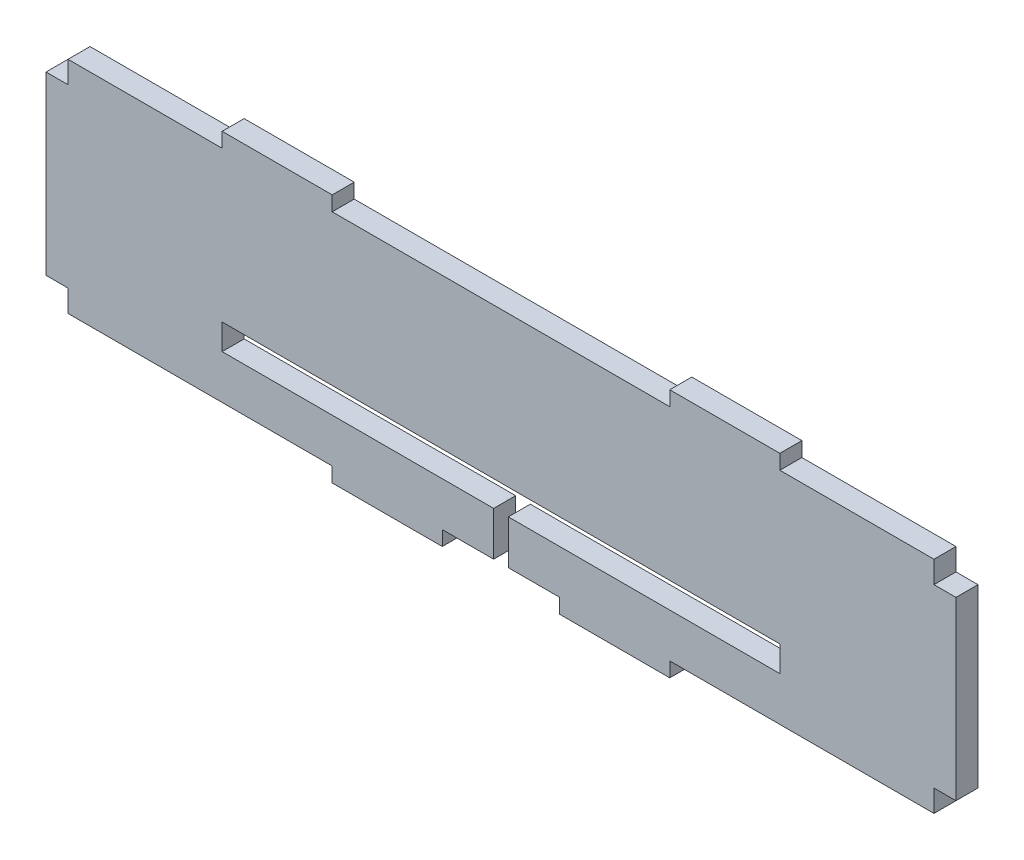
SolidWorks part; units mm, degrees
ref_plane "Front Plane" through (0, 0, 0) normal (0, 0, 1) x (1, 0, 0)
ref_plane "Top Plane" through (0, 0, 0) normal (0, 1, 0) x (1, 0, 0)
ref_plane "Right Plane" through (0, 0, 0) normal (1, 0, 0) x (0, 0, -1)
sketch "Sketch1" plane through (0, 0, 0) normal (0, 0, 1) x (1, 0, 0)
  line L0 (0, 0) -> (0, 43717.3993) construction
  line L1 (-5.9695, 0) -> (43711.4297, 0) construction
  line L2 (3, 0) -> (42, 0)
  line L4 (3, 0) -> (3, 30)
  line L6 (127, 0) -> (127, 30)
  line L7 (42, 0) -> (42, -2)
  line L8 (42, -2) -> (57, -2)
  line L9 (57, -2) -> (57, 0)
  line L10 (57, 0) -> (73, 0)
  line L11 (73, 0) -> (73, -2)
  line L12 (73, -2) -> (88, -2)
  line L13 (88, -2) -> (88, 0)
  line L14 (88, 0) -> (127, 0)
  line L15 (65, 0) -> (65, -50000) construction
  line L16 (27, 9.5) -> (103, 9.5)
  line L17 (27, 9.5) -> (27, 6)
  line L19 (103, 9.5) -> (103, 6)
  line L20 (66, 0) -> (66, 6)
  line L21 (64, 0) -> (66, 0)
  line L22 (64, 0) -> (64, 6)
  line L25 (27, 6) -> (64, 6)
  line L26 (66, 6) -> (103, 6)
  line L27 (3, 30) -> (27, 30)
  line L29 (42, 30) -> (42, 32)
  line L30 (42, 32) -> (27, 32)
  line L31 (27, 30) -> (27, 32)
  line L32 (42, 30) -> (88, 30)
  line L33 (127, 30) -> (103, 30)
  line L34 (103, 30) -> (103, 32)
  line L35 (88, 32) -> (103, 32)
  line L36 (88, 30) -> (88, 32)
  line L37 (127, 3) -> (124, 3)
  line L38 (3, 0) -> (6, 0)
  line L39 (3, 0) -> (3, 3)
  line L40 (3, 3) -> (6, 3)
  line L41 (6, 0) -> (6, 3)
  line L42 (124, 0) -> (124, 3)
  line L43 (127, 0) -> (124, 0)
  line L44 (127, 0) -> (127, 3)
  line L45 (-14.82, 15) -> (49985.18, 15) construction
  line L46 (127, 30) -> (124, 30)
  line L47 (124, 30) -> (124, 27)
  line L48 (127, 27) -> (124, 27)
  line L49 (127, 30) -> (127, 27)
  line L50 (3, 27) -> (6, 27)
  line L51 (6, 30) -> (6, 27)
  line L52 (3, 30) -> (6, 30)
  line L53 (3, 30) -> (3, 27)
  point P36 (65, 30)
  dimension "D1" = 124
  dimension "D2" = 30
  dimension "D3" = 15
  dimension "D4" = 15
  dimension "D5" = 16
  dimension "D6" = 15
  dimension "D7" = 2
  dimension "D8" = 2
  dimension "D9" = 15
  dimension "D10" = 15
  dimension "D11" = 6
  dimension "D12" = 3.5
  dimension "D13" = 15
  dimension "D14" = 2
  dimension "D16" = 15
  dimension "D17" = 3
  dimension "D18" = 3
  dimension "D19" = 46
extrude "Boss-Extrude3" add sketch "Sketch1" along normal blind 3 contours L36 L32 L29 L30 L31 L27 L4 L2 L7 L8 L9 L10 L22 L25 L17 L16 L19 L26 L20 L11 L12 L13 L14 L6 L33 L34 L35 region at (65, 15.5878, 0)
